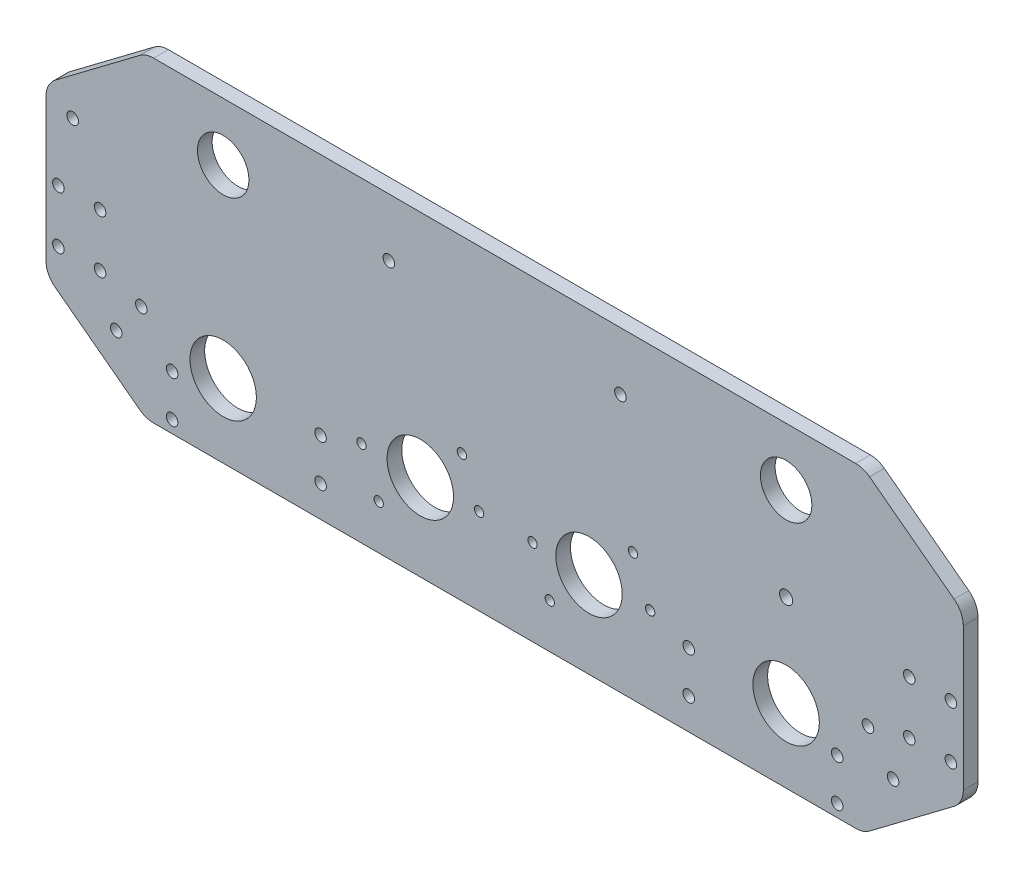
SolidWorks part; units mm, degrees
other "Marca1"
sketch "Croquis7" plane through (-185.6263, 143.9, 0) normal (-0.9207, 0.3803, -0.0878) x (0.0129, 0.2544, 0.967)
material "6061-O (SS)"
ref_plane "Alzado" through (0, 0, 0) normal (0, 0, 1) x (1, 0, 0)
ref_plane "Planta" through (0, 0, 0) normal (0, 1, 0) x (1, 0, 0)
ref_plane "Vista lateral" through (0, 0, 0) normal (1, 0, 0) x (0, 0, -1)
sketch "Croquis1" plane through (0, 0, 0) normal (0, 0, 1) x (1, 0, 0)
  line L0 (155, 0) -> (-155, 0)
  line L1 (-155, 0) -> (-198.1263, 32.498)
  line L2 (0, 127.4112) -> (0, -127.4112) construction
  line L3 (-198.1263, 32.498) -> (-198.1263, 104.0239)
  line L5 (-123.3669, 68.261) -> (123.3669, 68.261)
  line L6 (155, 0) -> (198.1263, 32.498)
  line L7 (198.1263, 32.498) -> (198.1263, 104.0239)
  line L9 (-155, 68.261) -> (-123.3669, 0) construction
  line L10 (-155, 0) -> (-123.3669, 0)
  line L11 (-155, 0) -> (-155, 68.261)
  line L12 (-155, 68.261) -> (-123.3669, 68.261)
  line L13 (-123.3669, 0) -> (-123.3669, 68.261)
  line L14 (-155, 0) -> (-123.3669, 68.261) construction
  line L15 (-155, 68.261) -> (-198.1263, 68.261)
  line L16 (123.3669, 68.261) -> (198.1263, 68.261)
  line L17 (155, 136.5219) -> (198.1263, 104.0239)
  line L18 (155, 136.5219) -> (-155, 136.5219)
  line L19 (-155, 136.5219) -> (-198.1263, 104.0239)
  point P4 (0, 0)
  point P9 (0, 0)
  point P13 (0, 68.261)
  dimension "D1" = 310
  dimension "D2" = 143
  dimension "D3" = 32.498
  dimension "D4" = 71.5259
extrude "Saliente-Extruir1" add sketch "Croquis1" along normal blind 6.35 contours L13 L0 L6 L7 L5 | L11 L12 L3 L1 | L0 L13 L12 L11 | L1 L3 L19 L18 L17 L7 L6 L0 region at (32.5516, 34.899, 0) region at (-139.1834, 34.1305, 0) region at (-174.3177, 41.4089, 0)
sketch "Croquis2" plane through (0, 0, 6.35) normal (0, 0, 1) x (1, 0, 0)
  line L0 (0, 0) -> (0, 68.261) construction
  line L1 (-155, 0) -> (-97.6848, 0) construction
  line L4 (-198.1263, 32.498) -> (-198.1263, 104.0239) construction
  line L5 (155, 0) -> (-155, 0) construction
  line L13 (-90.6044, 57.15) -> (-152.5804, 57.15)
  line L14 (-90.6044, 57.15) -> (-90.6044, 6.35)
  line L15 (-90.6044, 6.35) -> (-152.5804, 6.35)
  line L16 (-152.5804, 57.15) -> (-152.5804, 6.35)
  line L17 (-90.6044, 57.15) -> (-152.5804, 6.35) construction
  line L18 (-90.6044, 6.35) -> (-152.5804, 57.15) construction
  circle A0 centre (-121.5924, 31.75) radius 14.345
  circle A1 centre (121.5924, 31.75) radius 14.345
  circle A4 centre (-51.5924, 45.4) radius 45.5 construction
  circle A5 centre (-51.5924, 45.4) radius 4.8593
  point P6 (-121.5924, 31.75)
  dimension "D1" = 28.69
  dimension "D3" = 91
  dimension "D4" = 76.5339
  dimension "D5" = 70
  dimension "D2" = 61.976
  dimension "D6" = 45.4
  dimension "D7" = 31.75
  dimension "D8" = 31.75
  dimension "D9" = 50.8
  dimension "D10" = 33.4076
fillet "Redondeo1" radius 10 8 edges at (-198.1263, 32.498, 3.175) (198.1263, 32.498, 3.175) (155, 0, 3.175) (-155, 0, 3.175) (155, 136.5219, 3.175) (198.1263, 104.0239, 3.175) (-155, 136.5219, 3.175) (-198.1263, 104.0239, 3.175)
extrude "Cortar-Extruir1" cut sketch "Croquis2" against normal blind 10 contours A0 | A1
sketch "Croquis3" plane through (0, 0, 6.35) normal (0, 0, 1) x (1, 0, 0)
  line L0 (-50.0924, 67.9) -> (-50.0924, 105.9) construction
  circle A0 centre (-50.0924, 45.4) radius 22.5 construction
  circle A2 centre (-50.0924, 105.9) radius 36.5
  circle A3 centre (-50.0924, 105.9) radius 38
  dimension "D1" = 45
  dimension "D3" = 73
  dimension "D2" = 38
sketch "Croquis8" plane through (0, 0, 6.35) normal (0, 0, 1) x (1, 0, 0)
  line L0 (151.654, 0) -> (-151.654, 0) construction
  line L1 (-63.4934, 74.4) -> (-9.3914, 74.4) construction
  line L2 (-63.4934, 74.4) -> (-63.4934, 0) construction
  line L3 (-63.4934, 0) -> (-9.3914, 0) construction
  line L4 (-9.3914, 74.4) -> (-9.3914, 0) construction
  line L5 (-63.4934, 74.4) -> (-9.3914, 0) construction
  line L6 (0, 0) -> (0, 136.5219) construction
  line L7 (151.654, 136.5219) -> (-151.654, 136.5219) construction
  line L8 (-61.8424, 37.2) -> (-11.0424, 37.2) construction
  line L9 (-54.4029, 19.2395) -> (-18.4819, 55.1605) construction
  circle A1 centre (-36.4424, 37.2) radius 37 construction
  circle A2 centre (-36.4424, 37.2) radius 14.345
  circle A3 centre (36.4424, 37.2) radius 14.345
  circle A4 centre (-36.4424, 37.2) radius 25.4 construction
  circle A10 centre (12.0572, 37.2) radius 2.01
  circle A11 centre (19.4967, 19.2395) radius 2.01
  circle A12 centre (62.8572, 37.2) radius 2.01
  circle A13 centre (55.4177, 55.1605) radius 2.01
  circle A14 centre (-18.4819, 55.1605) radius 2.02
  circle A15 centre (-11.0424, 37.2) radius 2.02
  circle A16 centre (-54.4029, 19.2395) radius 2.02
  circle A17 centre (-61.8424, 37.2) radius 2.02
  circle A18 centre (-121.5924, 31.75) radius 14.345
  point P20 (-36.4424, 37.2)
  point P23 (-36.4424, 37.2)
  dimension "D1" = 54.102
  dimension "D3" = 74
  dimension "D4" = 28.69
  dimension "D5" = 50.8
  dimension "D7" = 4.04
  dimension "D8" = 85.15
  dimension "D2" = 74.4
  dimension "D6" = 45
extrude "Cortar-Extruir2" cut sketch "Croquis8" against normal through all both and the other way through all
chamfer "Chaflán3" distance 1 angle 45 8 edges at (-52.3829, 19.2395, 0) (-59.8224, 37.2, 0) (-16.4619, 55.1605, 0) (-9.0224, 37.2, 0) (10.0472, 37.2, 0) (17.4867, 19.2395, 0) (53.4077, 55.1605, 0) (60.8472, 37.2, 0)
sketch "Croquis9" plane through (0, 0, 0) normal (0, 0, -1) x (-1, 0, 0)
  line L0 (0, 0) -> (0, 136.5219) construction
  line L1 (-151.654, 136.5219) -> (151.654, 136.5219) construction
  line L2 (-121.5924, 31.75) -> (-121.5924, 111.5219) construction
  line L3 (121.5924, 31.75) -> (121.5924, 111.5219) construction
  line L4 (-121.5924, 111.5219) -> (121.5924, 111.5219) construction
  circle A0 centre (0, 111.5219) radius 11.1125 construction
  circle A1 centre (-121.5924, 111.5219) radius 11.1125
  circle A2 centre (121.5924, 111.5219) radius 11.1125
  dimension "D1" = 22.225
  dimension "D2" = 25
  dimension "D3" = 25
  dimension "D4" = 243.1848
extrude "Cortar-Extruir3" cut sketch "Croquis9" against normal blind 10
sketch "Croquis10" plane through (0, 0, 0) normal (0, 0, -1) x (-1, 0, 0)
  line L0 (-121.5924, 111.5219) -> (121.5924, 111.5219) construction
  line L1 (0, 111.5219) -> (0, 136.5219) construction
  line L2 (-151.654, 136.5219) -> (151.654, 136.5219) construction
  line L3 (50, 111.5219) -> (50, 136.5219) construction
  line L4 (-121.5924, 111.5219) -> (-121.5924, 31.75) construction
  line L5 (121.5924, 111.5219) -> (186.5924, 111.5219) construction
  line L6 (186.5924, 111.5219) -> (186.5924, 96.5219) construction
  circle A0 centre (-50, 111.5219) radius 2.5
  circle A1 centre (50, 111.5219) radius 2.5
  circle A3 centre (-121.5924, 71.4619) radius 2.8432
  circle A4 centre (186.5924, 96.5219) radius 2.5
  dimension "D1" = 5
  dimension "D2" = 40.06
  dimension "D4" = 65
  dimension "D3" = 50
  dimension "D6" = 5
  dimension "D5" = 15
extrude "Cortar-Extruir4" cut sketch "Croquis10" against normal blind 10
sketch "Croquis11" plane through (0, 0, 6.35) normal (0, 0, 1) x (1, 0, 0)
  line L0 (-143.654, 31.85) -> (-143.654, 0) construction
  line L1 (-151.654, 0) -> (-135.654, 0) construction
  line L2 (-151.654, 0) -> (-151.654, 31.85) construction
  line L3 (-151.654, 31.85) -> (-135.654, 31.85) construction
  line L4 (-135.654, 0) -> (-135.654, 31.85) construction
  line L5 (-79.5224, 0) -> (-79.5224, 51.998) construction
  line L6 (151.654, 0) -> (-151.654, 0) construction
  line L7 (0, 0) -> (0, 136.5219) construction
  line L8 (-87.5224, 40) -> (-71.5224, 40) construction
  line L9 (-87.5224, 40) -> (-87.5224, 0) construction
  line L10 (-87.5224, 0) -> (-71.5224, 0) construction
  line L11 (-71.5224, 40) -> (-71.5224, 0) construction
  line L12 (-87.5224, 40) -> (-71.5224, 0) construction
  line L13 (-87.5224, 0) -> (-71.5224, 40) construction
  line L14 (151.654, 136.5219) -> (-151.654, 136.5219) construction
  line L15 (-198.1263, 37.4838) -> (-198.1263, 99.0381) construction
  line L16 (-198.1263, 37.4838) -> (-166.2763, 37.4838) construction
  line L17 (-198.1263, 37.4838) -> (-198.1263, 53.4838) construction
  line L18 (-198.1263, 53.4838) -> (-166.2763, 53.4838) construction
  line L19 (-166.2763, 37.4838) -> (-166.2763, 53.4838) construction
  line L20 (-166.2763, 45.4838) -> (-198.1263, 45.4838) construction
  line L21 (-198.1263, 68.261) -> (-164.4763, 68.261) construction
  line L22 (-174.7763, 45.4838) -> (-174.7763, 68.261) construction
  line L23 (-192.7763, 45.4838) -> (-192.7763, 68.261) construction
  line L24 (-175.9083, 15.7556) -> (-151.8357, 47.701) construction
  line L26 (-194.1445, 29.4975) -> (-157.6722, 2.0136) construction
  circle A0 centre (-143.654, 23.35) radius 2.5
  circle A1 centre (-143.654, 5.35) radius 2.5
  circle A2 centre (-121.5924, 31.75) radius 14.345 construction
  circle A3 centre (-36.4424, 37.2) radius 14.3149 construction
  circle A4 centre (-79.5224, 31.5) radius 2.5
  circle A5 centre (-79.5224, 13.5) radius 2.5
  circle A6 centre (143.654, 5.35) radius 2.5
  circle A7 centre (143.654, 23.35) radius 2.5
  circle A8 centre (79.5224, 13.5) radius 2.5
  circle A9 centre (79.5224, 31.5) radius 2.5
  arc A10 (-198.1263, 37.4838) -> (-194.1445, 29.4975) centre (-188.1263, 37.4838) ccw construction
  circle A11 centre (-174.7763, 45.4838) radius 2.5
  circle A12 centre (-192.7763, 45.4838) radius 2.5
  circle A13 centre (-174.7763, 68.261) radius 2.5
  circle A14 centre (-192.7763, 68.261) radius 2.5
  circle A15 centre (174.7763, 45.4838) radius 2.5
  circle A16 centre (192.7763, 45.4838) radius 2.5
  circle A17 centre (192.7763, 68.261) radius 2.5
  circle A18 centre (174.7763, 68.261) radius 2.5
  circle A23 centre (-156.9512, 40.9126) radius 2.5
  circle A24 centre (-167.7838, 26.5371) radius 2.5
  circle A25 centre (167.7838, 26.5371) radius 2.5
  circle A26 centre (156.9512, 40.9126) radius 2.5
  point P21 (-79.5224, 20)
  dimension "D3" = 5
  dimension "D4" = 8.5
  dimension "D5" = 18
  dimension "D6" = 85.15
  dimension "D10" = 8.5
  dimension "D11" = 18
  dimension "D14" = 5
  dimension "D15" = 8.5
  dimension "D16" = 18
  dimension "D17" = 5
  dimension "D18" = 5
  dimension "D19" = 5
  dimension "D22" = 5
  dimension "D23" = 8.5
  dimension "D24" = 18
  dimension "D21" = 5
  dimension "D1" = 31.85
  dimension "D2" = 16
  dimension "D7" = 42.07
  dimension "D8" = 40
  dimension "D9" = 16
  dimension "D12" = 16
  dimension "D13" = 31.85
  dimension "D20" = 40
extrude "Cortar-Extruir5" cut sketch "Croquis11" against normal blind 10
